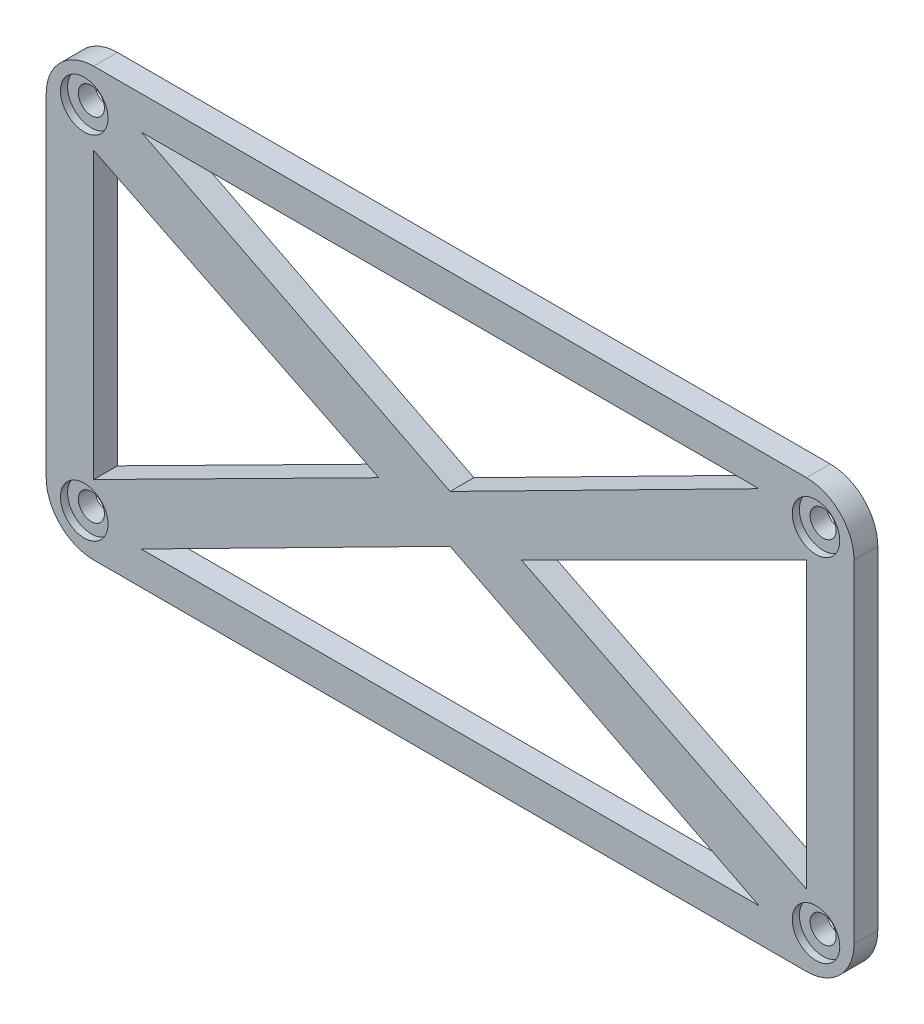
SolidWorks part; units mm, degrees
ref_plane "前视基准面" through (0, 0, 0) normal (0, 0, 1) x (1, 0, 0)
ref_plane "上视基准面" through (0, 0, 0) normal (0, 1, 0) x (1, 0, 0)
ref_plane "右视基准面" through (0, 0, 0) normal (1, 0, 0) x (0, 0, -1)
sketch "草图1" plane through (0, 0, 0) normal (0, 0, 1) x (1, 0, 0)
  line L1 (-72.5741, 45.4874) -> (77.4259, 45.4874)
  line L2 (-82.5741, 35.4874) -> (-82.5741, -34.5126)
  line L3 (-72.5741, -44.5126) -> (77.4259, -44.5126)
  line L4 (87.4259, 35.4874) -> (87.4259, -34.5126)
  arc A0 (-72.5741, 45.4874) -> (-82.5741, 35.4874) centre (-72.5741, 35.4874) ccw
  arc A1 (-72.5741, -44.5126) -> (-82.5741, -34.5126) centre (-72.5741, -34.5126) cw
  arc A2 (87.4259, 35.4874) -> (77.4259, 45.4874) centre (77.4259, 35.4874) ccw
  arc A3 (87.4259, -34.5126) -> (77.4259, -44.5126) centre (77.4259, -34.5126) cw
  dimension "D1" = 10
  dimension "D2" = 10
  dimension "D3" = 10
  dimension "D4" = 10
  dimension "D5" = 90
  dimension "D6" = 170
extrude "凸台-拉伸1" add sketch "草图1" along normal blind 5
ref_plane "for screw hole" through (0, 0, 5) normal (0, 0, 1) x (1, 0, 0)
sketch "草图2" plane through (0, 0, 5) normal (0, 0, 1) x (1, 0, 0)
  line L0 (77.4259, 45.4874) -> (-72.5741, 45.4874) construction
  line L1 (-82.5741, 35.4874) -> (-82.5741, -34.5126) construction
  line L2 (-72.5741, -44.5126) -> (77.4259, -44.5126) construction
  line L3 (87.4259, -34.5126) -> (87.4259, 35.4874) construction
  line L4 (-62.5741, 38.4874) -> (2.4259, 5.4874)
  line L6 (-72.5741, 30.1561) -> (-12.5741, 0.4874)
  line L8 (2.4259, -4.5126) -> (-62.5741, -37.5126)
  line L10 (67.4259, -37.5126) -> (2.4259, -4.5126)
  line L12 (-72.5741, -29.8439) -> (-12.5741, 0.4874)
  line L13 (-72.5741, 30.1561) -> (-72.5741, -29.8439)
  line L15 (-62.5741, -37.5126) -> (67.4259, -37.5126)
  line L17 (67.4259, 38.4874) -> (2.4259, 5.4874)
  line L19 (-62.5741, 38.4874) -> (67.4259, 38.4874)
  line L21 (17.4259, 0.4874) -> (77.4259, 30.4874)
  line L25 (17.4259, 0.4874) -> (77.4259, -29.5126)
  line L26 (77.4259, -29.5126) -> (77.4259, 30.4874)
  circle A0 centre (-74.5741, 37.4874) radius 2.75
  circle A1 centre (-74.5741, -36.5126) radius 2.75
  circle A2 centre (79.4259, 37.4874) radius 2.75
  circle A3 centre (79.4259, -36.5126) radius 2.75
  point P19 (-62.5741, 30.4874)
  point P23 (77.4259, 30.4874)
  point P38 (2.4259, 5.4874)
  point P39 (-12.5741, 0.4874)
  point P40 (67.4259, 38.4874)
  point P41 (-62.5741, 38.4874)
  point P42 (2.4259, -4.5126)
  point P43 (17.4259, 0.4874)
  point P45 (-72.5741, -29.8439)
  point P46 (-62.5741, -37.5126)
  point P47 (67.4259, -37.5126)
  point P48 (77.4259, -29.5126)
  dimension "D2" = 5.5
  dimension "D3" = 5.5
  dimension "D4" = 5.5
  dimension "D8" = 8
  dimension "D9" = 8
  dimension "D10" = 8
  dimension "D11" = 5.5
  dimension "D14" = 70
  dimension "D5" = 8
  dimension "D6" = 8
  dimension "D7" = 8
  dimension "D12" = 8
  dimension "D13" = 8
  dimension "D15" = 70
  dimension "D16" = 40
  dimension "D17" = 45
  dimension "D18" = 45
  dimension "D19" = 60
  dimension "D20" = 7
  dimension "D21" = 7
  dimension "D22" = 20
  dimension "D23" = 20
  dimension "D24" = 20
  dimension "D25" = 10
  dimension "D26" = 7
  dimension "D27" = 20
  dimension "D28" = 15
  dimension "D29" = 15
  dimension "D30" = 10
  dimension "D31" = 10
  dimension "D32" = 15
  dimension "D33" = 7
  dimension "D34" = 20
extrude "切除-拉伸1" cut sketch "草图2" against normal blind 10 and the other way blind 39
ref_plane "for outer screw hole" through (0, 0, 5) normal (0, 0, 1) x (1, 0, 0)
sketch "草图3" plane through (0, 0, 5) normal (0, 0, 1) x (1, 0, 0)
  circle A0 centre (-74.5741, 37.4874) radius 5
  circle A1 centre (79.4259, 37.4874) radius 5
  circle A2 centre (79.4259, -36.5126) radius 5
  circle A3 centre (-74.5741, -36.5126) radius 5
  dimension "D1" = 10
  dimension "D2" = 10
  dimension "D3" = 10
  dimension "D4" = 10
extrude "切除-拉伸2" cut sketch "草图3" against normal blind 1.5
ref_plane "for stands" through (0, 0, 5) normal (0, 0, 1) x (1, 0, 0)
